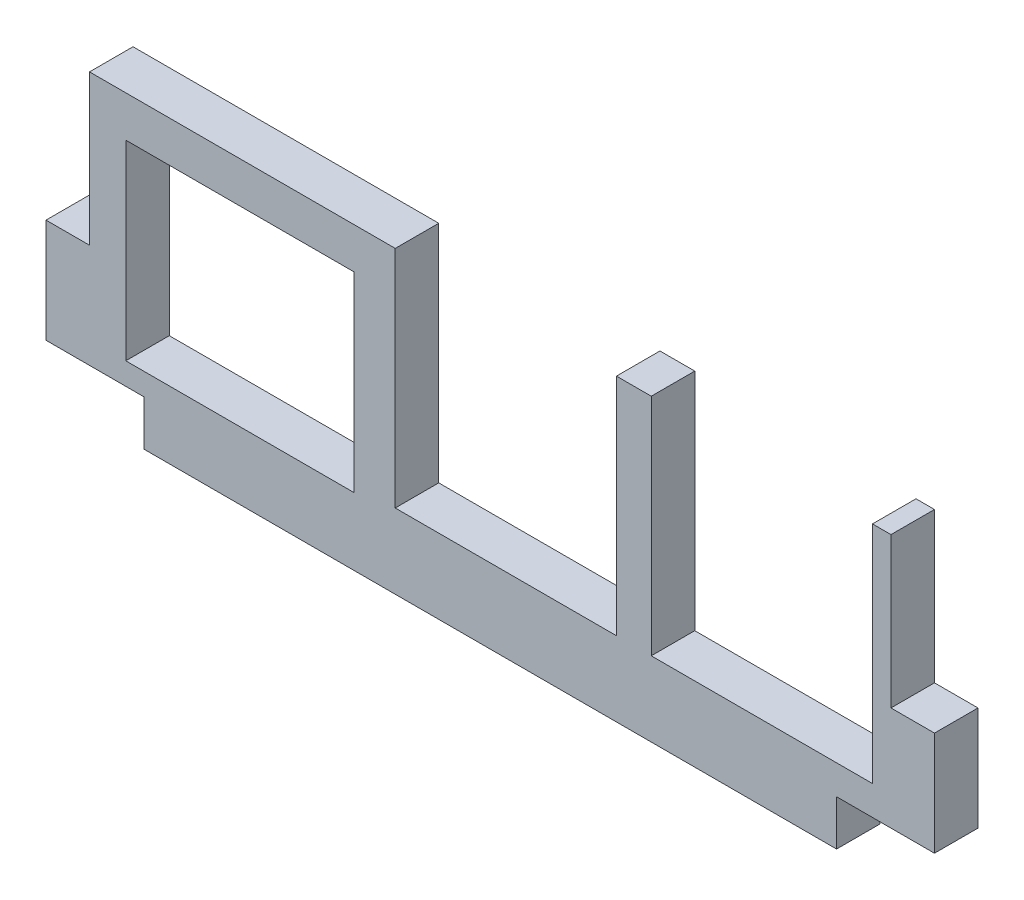
SolidWorks part; units mm, degrees
ref_plane "Front Plane" through (0, 0, 0) normal (0, 0, 1) x (1, 0, 0)
ref_plane "Top Plane" through (0, 0, 0) normal (0, 1, 0) x (1, 0, 0)
ref_plane "Right Plane" through (0, 0, 0) normal (1, 0, 0) x (0, 0, -1)
sketch "Sketch1" plane through (0, 0, 0) normal (0, 0, 1) x (1, 0, 0)
  line L0 (-3.048, 12.0142) -> (0, 12.0142) construction
  line L1 (-3.048, 12.0142) -> (-3.048, 4.7244) construction
  line L2 (3.81, 1.5494) -> (3.81, 4.7244) construction
  line L3 (3.81, 1.5494) -> (52.324, 1.5494) construction
  line L4 (52.324, 1.5494) -> (52.324, 4.7244) construction
  line L5 (59.182, 12.0142) -> (56.134, 12.0142) construction
  line L6 (59.182, 4.7244) -> (59.182, 12.0142) construction
  line L7 (-3.048, 12.0142) -> (0, 12.0142)
  line L8 (-3.048, 12.0142) -> (-3.048, 4.7244)
  line L9 (3.81, 1.5494) -> (3.81, 4.7244)
  line L10 (3.81, 1.5494) -> (52.324, 1.5494)
  line L11 (52.324, 1.5494) -> (52.324, 4.7244)
  line L12 (59.182, 12.0142) -> (56.134, 12.0142)
  line L13 (59.182, 4.7244) -> (59.182, 12.0142)
  line L14 (-3.048, 4.7244) -> (3.81, 4.7244)
  line L15 (52.324, 4.7244) -> (59.182, 4.7244)
  line L16 (0, 12.0142) -> (0, 19.6596)
  line L17 (0, 27.2034) -> (0, 4.7244) construction
  line L18 (0, 19.6596) -> (2.54, 19.6596)
  line L19 (2.54, 19.6596) -> (2.54, 6.2738)
  line L20 (2.54, 6.2738) -> (18.542, 6.2738)
  line L21 (18.542, 6.2738) -> (18.542, 22.5298)
  line L22 (18.542, 22.5298) -> (21.4122, 22.5298)
  line L23 (21.4122, 22.5298) -> (21.4122, 6.7818)
  line L24 (21.4122, 6.7818) -> (36.9062, 6.7818)
  line L25 (36.9062, 6.7818) -> (36.9062, 22.5298)
  line L26 (36.9062, 22.5298) -> (39.3446, 22.5298)
  line L27 (39.3446, 22.5298) -> (39.3446, 6.7818)
  line L28 (39.3446, 6.7818) -> (54.8386, 6.7818)
  line L29 (54.8386, 6.7818) -> (54.8386, 22.5298)
  line L30 (54.8386, 22.5298) -> (56.134, 22.5298)
  line L31 (56.134, 27.2034) -> (56.134, 4.7244) construction
  line L32 (56.134, 22.5298) -> (56.134, 12.0142)
  dimension "D1" = 14.9352
  dimension "D2" = 2.54
  dimension "D3" = 2.8702
  dimension "D4" = 2.4384
  dimension "D5" = 15.494
  dimension "D6" = 16.002
  dimension "D7" = 1.5494
  dimension "D8" = 15.748
  dimension "D9" = 2.0574
extrude "Boss-Extrude1" add sketch "Sketch1" along normal blind 3.048
sketch "Sketch2" plane through (0, 0, 3.048) normal (0, 0, 1) x (1, 0, 0)
  line L1 (0, 19.6596) -> (18.542, 19.6596)
  line L2 (0, 19.6596) -> (0, 22.5298)
  line L3 (0, 22.5298) -> (18.542, 22.5298)
  line L4 (18.542, 19.6596) -> (18.542, 22.5298)
extrude "Boss-Extrude2" add sketch "Sketch2" against normal up to vertex (3.048 mm away) up to point (18.542, 22.5298, 0)
